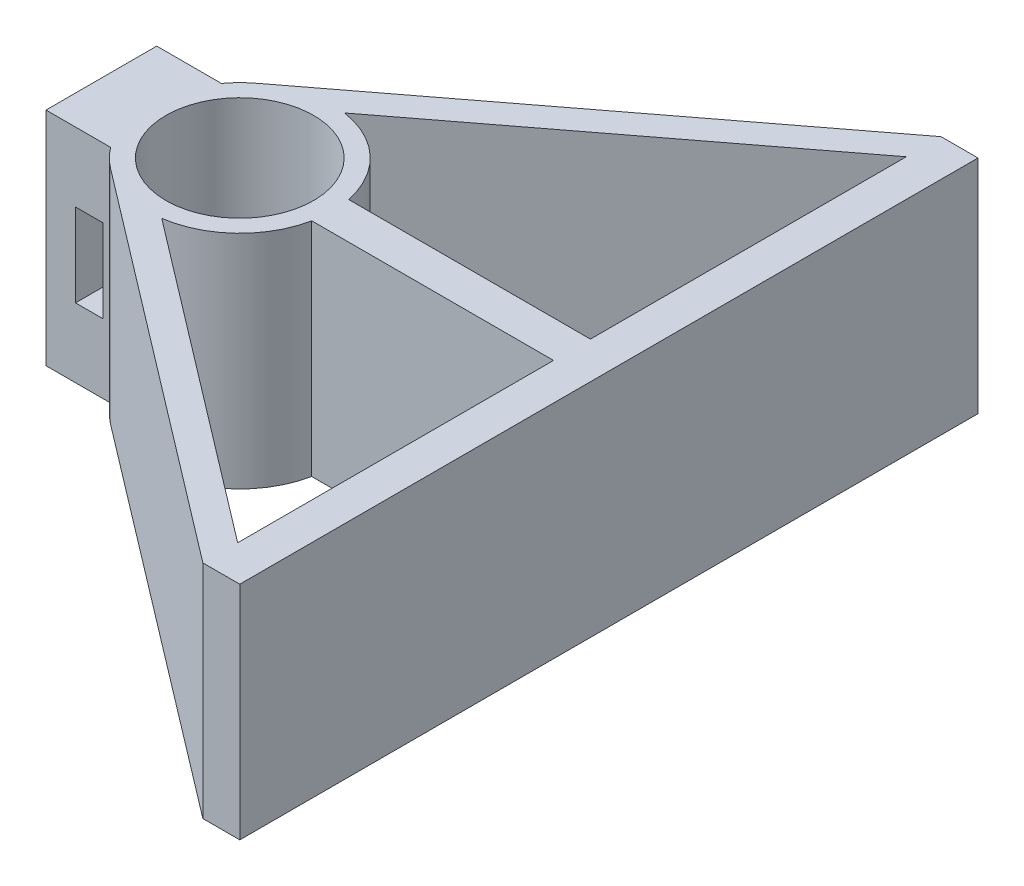
SolidWorks part; units mm, degrees
ref_plane "Front Plane" through (0, 0, 0) normal (0, 0, 1) x (1, 0, 0)
ref_plane "Top Plane" through (0, 0, 0) normal (0, 1, 0) x (1, 0, 0)
ref_plane "Right Plane" through (0, 0, 0) normal (1, 0, 0) x (0, 0, -1)
sketch "Sketch1" plane through (0, 0, 0) normal (0, 1, 0) x (1, 0, 0)
  line L0 (0, 0) -> (-14.5636, 0) construction
  line L1 (-4, 3) -> (-7.5, 3)
  line L2 (-7.5, 3) -> (-7.5, -3)
  line L3 (-4, -3) -> (-7.5, -3)
  line L4 (20, -1.9056) -> (20, 20)
  line L5 (20, 20) -> (18, 20)
  line L6 (18, 20) -> (-3.0302, 3.9772)
  line L7 (4.899, 1) -> (18, 1)
  line L8 (18, 1) -> (18, 18.1142)
  line L9 (18, 18.1142) -> (0.7191, 4.948)
  line L10 (4.899, -1) -> (18, -1)
  line L11 (20, -1.9056) -> (20, -20)
  line L12 (20, -20) -> (18, -20)
  line L13 (18, -1) -> (18, -18.1142)
  line L14 (18, -18.1142) -> (0.7191, -4.948)
  line L15 (18, -20) -> (-3.0302, -3.9772)
  circle A0 centre (0, 0) radius 4
  arc A1 (-4, -3) -> (-3.0302, -3.9772) centre (0, 0) ccw
  arc A2 (4.899, 1) -> (0.7191, 4.948) centre (0, 0) ccw
  arc A3 (0.7191, -4.948) -> (4.899, -1) centre (0, 0) ccw
  arc A4 (-3.0302, 3.9772) -> (-4, 3) centre (0, 0) ccw
  point P10 (-7.5, 0)
  point P25 (13.0223, 2.2861)
  point P26 (0, 0)
  dimension "D1" = 8
  dimension "D2" = 1
  dimension "D10" = 20
  dimension "D3" = 6
  dimension "D4" = 7.5
  dimension "D5" = 2
  dimension "D6" = 2
  dimension "D7" = 1.5
  dimension "D8" = 40
  dimension "D9" = 2
extrude "Boss-Extrude1" add sketch "Sketch1" along normal blind 6 and the other way blind 6
sketch "Sketch2" plane through (0, 0, -3) normal (0, 0, -1) x (-1, 0, 0)
  line L0 (-6.9549, 0) -> (16.7857, 0) construction
  line L1 (4.4, -2.25) -> (4.4, 2.25)
  line L2 (4.4, 2.25) -> (5.9, 2.25)
  line L3 (5.9, 2.25) -> (5.9, -2.25)
  line L4 (4.4, -2.25) -> (5.9, -2.25)
  point P8 (5.9, 0)
  point P9 (4.4, 0)
  dimension "D1" = 4.5
  dimension "D2" = 4.4
  dimension "D3" = 1.5
extrude "Cut-Extrude1" cut sketch "Sketch2" against normal through all
